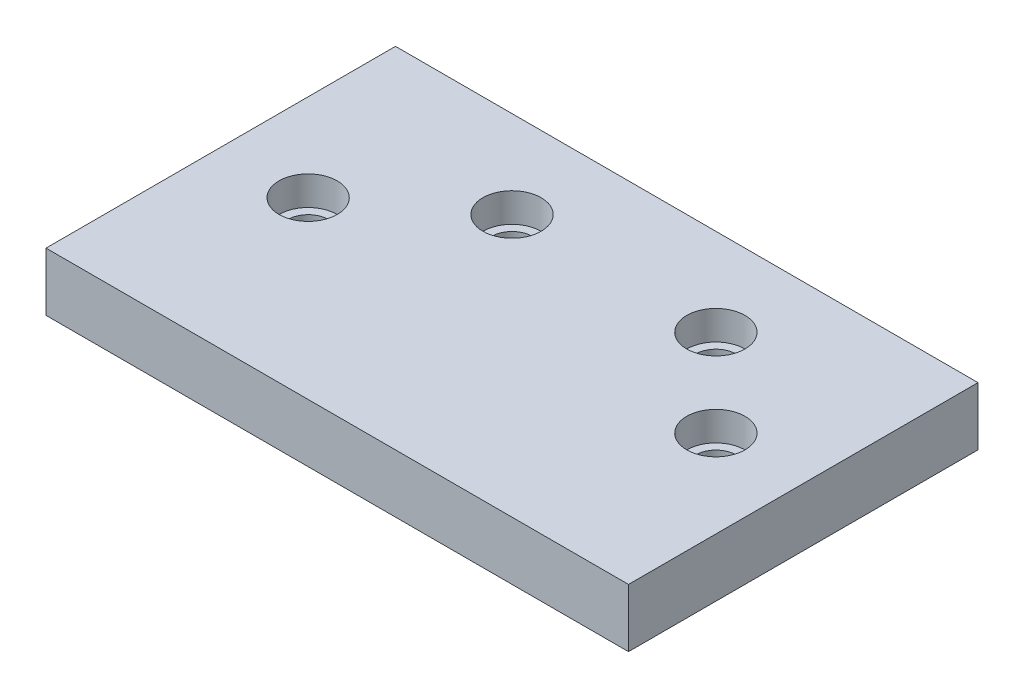
SolidWorks part; units mm, degrees
ref_plane "前视基准面" through (0, 0, 0) normal (0, 0, 1) x (1, 0, 0)
ref_plane "上视基准面" through (0, 0, 0) normal (0, 1, 0) x (1, 0, 0)
ref_plane "右视基准面" through (0, 0, 0) normal (1, 0, 0) x (0, 0, -1)
other "Configuration Table"
sketch "草图1" plane through (0, 0, 0) normal (0, 1, 0) x (1, 0, 0)
  line L1 (0, 0) -> (20, 0)
  line L2 (0, 0) -> (0, -12)
  line L3 (0, -12) -> (20, -12)
  line L4 (20, 0) -> (20, -12)
  circle A0 centre (3, -6) radius 0.7
  circle A1 centre (7, -3) radius 0.7
  circle A2 centre (14, -3) radius 0.7
  circle A3 centre (17, -6) radius 0.7
  circle A4 centre (3, -6) radius 1
  circle A5 centre (7, -3) radius 1
  circle A6 centre (14, -3) radius 1
  circle A7 centre (17, -6) radius 1
  point P17 (0, 0)
  point P18 (0, 0)
  point P19 (0, 0)
  point P20 (0, 0)
  dimension "D3" = 1.4
  dimension "D4" = 2
  dimension "D1" = 12
  dimension "D2" = 20
extrude "凸台-拉伸1" add sketch "草图1" along normal blind 2 contours L1 L4 L3 L2 | A2 | A3 | A1 | A0
extrude "切除-拉伸1" cut sketch "草图1<3>" against normal blind 1 from surface contours A4 | A5 | A6 | A7 starting at face at (7, 2, 3.7)
sketch "草图1<3>" plane through (0, 0, 0) normal (0, 1, 0) x (1, 0, 0) same geometry as "草图1"
